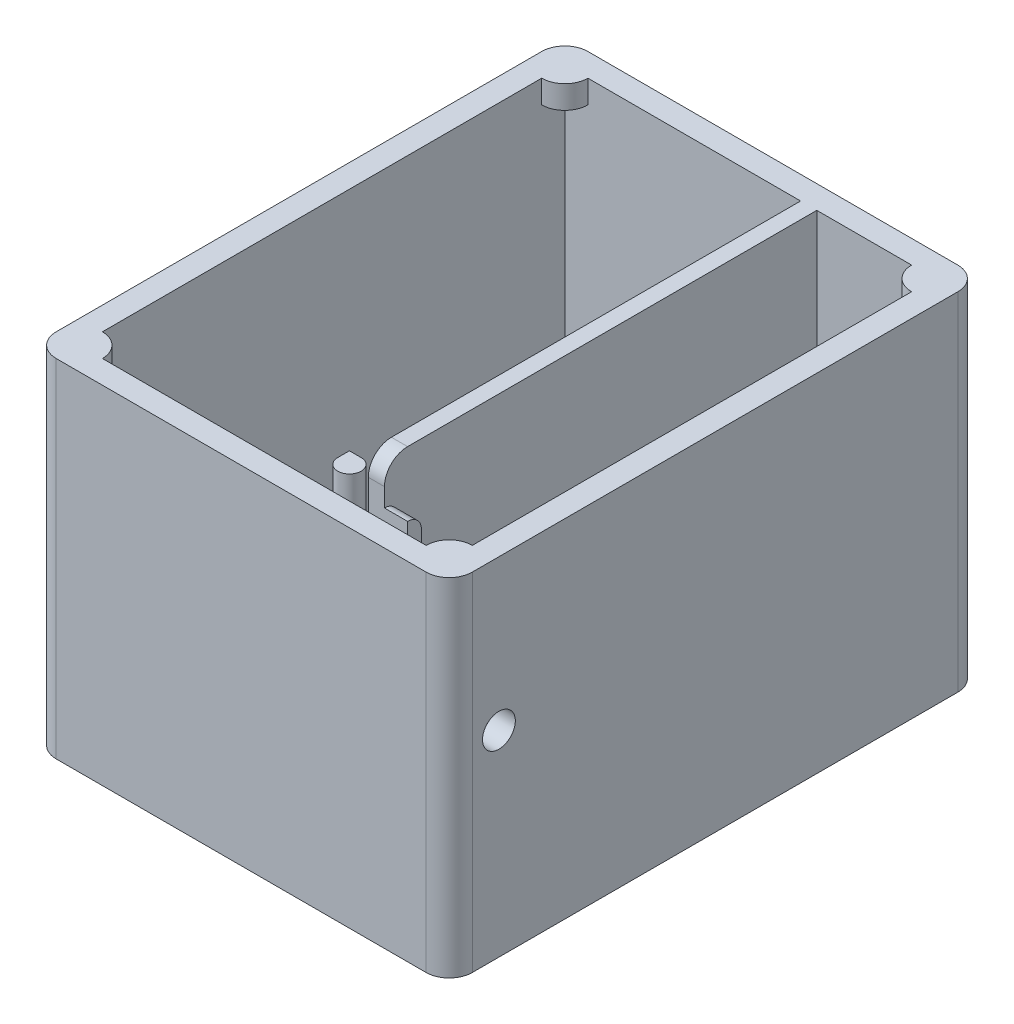
SolidWorks part; units mm, degrees
ref_plane "Front" through (0, 0, 0) normal (0, 0, 1) x (1, 0, 0)
ref_plane "Top" through (0, 0, 0) normal (0, 1, 0) x (1, 0, 0)
ref_plane "Right" through (0, 0, 0) normal (1, 0, 0) x (0, 0, -1)
sketch "Sketch1" plane through (0, 0, 0) normal (0, 1, 0) x (1, 0, 0)
  line L1 (-45, 57.5) -> (45, 57.5)
  line L2 (-45, 57.5) -> (-45, -57.5)
  line L3 (-45, -57.5) -> (45, -57.5)
  line L4 (45, 57.5) -> (45, -57.5)
  line L5 (-45, 57.5) -> (45, -57.5) construction
  line L6 (-45, -57.5) -> (45, 57.5) construction
  line L11 (-38.7302, 49.4886) -> (40.1958, -51.3613) construction
  point P0 (0, 0)
  point P5 (0, 0)
extrude "Boss-Extrude1" add sketch "Sketch1" along normal blind 70 contours L2 L1 L4 L3
sketch "Sketch2" plane through (0, 70, 0) normal (0, 1, 0) x (1, 0, 0)
  line L0 (40, -38) -> (40, -41) construction
  line L9 (14.5, 57.5) -> (14.5, -57.5) construction
  line L10 (40, 52.5) -> (14.5, 52.5)
  line L11 (40, 52.5) -> (40, -38)
  line L12 (40, -38) -> (14.5, -38)
  line L13 (40, 50) -> (40, 57.5) construction
  line L14 (14.5, 52.5) -> (14.5, -38)
  line L15 (-45, -41) -> (45, -41) construction
  line L16 (-45, 57.5) -> (45, 57.5) construction
  line L17 (45, 57.5) -> (45, -57.5) construction
  line L18 (40, 57.5) -> (40, 52.5) construction
  line L19 (-45, 57.5) -> (-45, -57.5) construction
  line L20 (40, 57.5) -> (40, -57.5) construction
  line L21 (-45, -57.5) -> (45, -57.5) construction
  line L27 (40, -57.5) -> (40, -52.5) construction
  line L28 (45, -52.5) -> (-45, -52.5) construction
  line L29 (45, 52.5) -> (-45, 52.5) construction
  point P0 (0, 0)
sketch "Sketch3" [suppressed] plane through (0, 70.016, 0) normal (0, 1, 0) x (1, 0, 0)
sketch "Sketch4" [suppressed] plane through (0, 70.016, 0) normal (0, 1, 0) x (1, 0, 0)
sketch "Sketch6" plane through (0, 70, 0) normal (0, 1, 0) x (1, 0, 0)
  line L3 (8, -52.5) -> (40, -52.5)
  line L4 (40, -41) -> (40, -52.5)
  line L6 (40, -41) -> (8, -41)
  line L8 (8, -41) -> (8, -52.5)
extrude "Cut-Extrude2" cut sketch "Sketch6" against normal blind 65.5
sketch "Sketch22" plane through (40, 0, 0) normal (-1, 0, 0) x (0, 0, 1)
  line L0 (52.5, 4.5) -> (52.5, 42.5) construction
  line L1 (52.5, 42.5) -> (46.75, 42.5) construction
  circle A0 centre (46.75, 42.5) radius 3.55
extrude "Cut-Extrude11" cut sketch "Sketch22" against normal through all both and the other way through all
extrude "Cut-Extrude12" cut sketch "Sketch2" against normal blind 65.5
sketch "Sketch23" plane through (0, 0, 38) normal (0, 0, -1) x (-1, 0, 0)
  line L2 (-40, 4.5) -> (-35, 4.5) construction
  line L3 (-35, 4.5) -> (-35, 10.5) construction
  line L5 (-19.5, 66) -> (-35, 66)
  line L6 (-19.5, 66) -> (-19.5, 10.5)
  line L7 (-19.5, 10.5) -> (-35, 10.5)
  line L8 (-35, 66) -> (-35, 10.5)
extrude "Cut-Extrude13" cut sketch "Sketch23" against normal blind 3
sketch "Sketch24" plane through (0, 0, 38) normal (0, 0, -1) x (-1, 0, 0)
  line L0 (-14.5, 70) -> (-14.5, 19.5) construction
  line L1 (-14.5, 4.5) -> (-14.5, 19.5) construction
  line L6 (-1.0248, 22.3804) -> (-21.5174, 18) construction
  line L7 (-17.8035, 50.536) -> (-18.2248, 54.4939) construction
  line L8 (-7.4826, 21) -> (-21.5174, 21)
  line L9 (-7.4826, 21) -> (-7.4826, 18)
  line L10 (-7.4826, 18) -> (-21.5174, 18)
  line L11 (-21.5174, 21) -> (-21.5174, 18)
  line L12 (-7.4826, 21) -> (-21.5174, 18) construction
  line L13 (-7.4826, 18) -> (-21.5174, 21) construction
extrude "Cut-Extrude14" cut sketch "Sketch24" against normal blind 3
fillet "Fillet2" radius 5 1 edges at (-45, 35, 57.5) type face fillet first side face at (0, 35, 57.5) second side face at (-45, 42.5, 50.3)
fillet "Fillet3" radius 5 1 edges at (45, 35, 57.5) type face fillet first side face at (45, 42.5, 50.3) second side face at (2.5, 35, 57.5)
fillet "Fillet4" radius 5 1 edges at (45, 35, -57.5) type face fillet first side face at (45, 42.5, 50.3) second side face at (0, 35, -57.5)
fillet "Fillet5" radius 5 1 edges at (-45, 35, -57.5) type face fillet first side face at (-2.5, 35, -57.5) second side face at (-45, 42.5, 50.3)
sketch "Sketch33" plane through (0, 0, 0) normal (0, -1, 0) x (1, 0, 0)
  line L0 (-45, -52.5) -> (-45, 52.5) construction
  line L1 (45, 57.4997) -> (-45, 57.4997)
  line L2 (45, 57.4997) -> (45, -57.4997)
  line L3 (45, -57.4997) -> (-45, -57.4997)
  line L4 (-45, 57.4997) -> (-45, -57.4997)
  line L5 (45, 57.4997) -> (-45, -57.4997) construction
  line L6 (45, -57.4997) -> (-45, 57.4997) construction
  point P0 (0, 0)
sketch "Sketch36" plane through (0, 70, 0) normal (0, 1, 0) x (1, 0, 0)
  line L0 (40, 34.925) -> (45, 34.925) construction
  line L1 (40, -38) -> (40, 52.5) construction
  line L2 (45, 52.5) -> (45, -52.5) construction
  line L3 (33.0194, 57.5) -> (33.0194, 52.5) construction
  line L4 (-40, 57.5) -> (40, 57.5) construction
  line L5 (40, 52.5) -> (14.5, 52.5) construction
  line L6 (25.7963, -52.5) -> (25.7963, -57.5) construction
  line L7 (8, -52.5) -> (40, -52.5) construction
  line L8 (-40, -57.5) -> (40, -57.5) construction
sketch "Sketch37" plane through (0, 70, 0) normal (0, 1, 0) x (1, 0, 0)
  line L0 (-26.557, 57.5) -> (-26.557, 52.5) construction
  line L1 (-40, 57.5) -> (40, 57.5) construction
  line L2 (-45, 49.7069) -> (-40, 49.7069) construction
  line L3 (-45, 52.5) -> (-45, -52.5) construction
  line L4 (-26.557, 52.5) -> (-40, 52.5) construction
  line L5 (-40, 52.5) -> (-40, 49.7069) construction
  line L6 (4.7483, -57.5) -> (4.7483, -52.5) construction
  line L7 (-40, -57.5) -> (40, -57.5) construction
  line L8 (-40, 52.5) -> (9, 52.5) construction
  line L10 (-40, 52.5) -> (11, 52.5)
  line L11 (-40, 52.5) -> (-40, -52.5)
  line L12 (-40, -52.5) -> (11, -52.5)
  line L13 (11, 52.5) -> (11, -52.5)
extrude "Cut-Extrude15" cut sketch "Sketch37" against normal blind 65.5
ref_plane "Plane1" through (-40, 70, -57.5) normal (1, 0, 0) x (0, 0, -1)
sketch "Sketch39" plane through (0, 4.5, 0) normal (0, 1, 0) x (1, 0, 0)
  line L0 (-40, -52.5) -> (-40, 5.92) construction
  line L1 (-40, 52.5) -> (-40, -52.5) construction
  line L2 (-40, 5.92) -> (10.8, 5.92) construction
  line L3 (10.8, 5.92) -> (10.8, -52.5) construction
  line L4 (-40, -52.5) -> (40, -52.5) construction
  line L5 (10.8, -52.5) -> (-40, -52.5) construction
  line L6 (10.8, -52.5) -> (8.26, -52.5) construction
  line L7 (-40, -52.5) -> (-37.46, -52.5) construction
  line L8 (10.8, 5.92) -> (8.26, 5.92)
  line L9 (-40, 5.92) -> (-37.46, 5.92)
  line L10 (-40, 5.92) -> (-40, 3.38)
  line L11 (10.8, 3.38) -> (8.26, 3.38) construction
  line L12 (-37.46, -52.5) -> (-40, -52.5)
  line L13 (-40, -52.5) -> (-40, -49.96)
  line L14 (10.8, 5.92) -> (10.8, 3.38)
  line L15 (10.8, -52.5) -> (8.26, -52.5)
  line L16 (10.8, -52.5) -> (10.8, -49.96)
  arc A4 (10.8, 3.38) -> (8.26, 5.92) centre (8.26, 3.38) cw
  arc A5 (10.8, -49.96) -> (8.26, -52.5) centre (8.26, -49.96) ccw
  arc A6 (-40, 3.38) -> (-37.46, 5.92) centre (-37.46, 3.38) ccw
  arc A7 (-37.46, -52.5) -> (-40, -49.96) centre (-37.46, -49.96) ccw
  line M3 (-40, 52.5) -> (-40, -52.5)
  line M4 (-40, -52.5) -> (40, -52.5)
sketch "Sketch40" plane through (11, 0, 0) normal (-1, 0, 0) x (0, 0, 1)
  line L0 (41, 4.5) -> (41, 26) construction
  line L1 (41, 70) -> (41, 21) construction
extrude "Boss-Extrude3" add sketch "Sketch39" along normal blind 21.5 contours L16 A5 M4 | A6 L9 M3 | A4 L8 L14 | A7 L13 L12 region at (8.3861, 4.5, 50.0861) region at (-37.5861, 4.5, -3.5061)
sketch "Sketch43" plane through (0, 26, 0) normal (0, 1, 0) x (1, 0, 0)
  line L0 (10.8, 3.38) -> (8.26, 3.38) construction
sketch "Sketch44" plane through (0, 70, 0) normal (0, 1, 0) x (1, 0, 0)
  circle A0 centre (40, 52.5) radius 5
  circle A1 centre (-40, 52.5) radius 5
  circle A2 centre (-40, -52.5) radius 5
  circle A3 centre (40, -52.5) radius 5
extrude "Boss-Extrude4" add sketch "Sketch44" along normal blind 5
sketch "Sketch48" plane through (0, 70, 0) normal (0, 1, 0) x (1, 0, 0)
  line L0 (-40, -57.5) -> (40, -57.5) construction
  line L1 (40, 57.5) -> (-40, 57.5)
  line L2 (40, 57.5) -> (40, 52.5)
  line L3 (40, 52.5) -> (-40, 52.5)
  line L4 (-40, 57.5) -> (-40, 52.5)
  line L5 (40, 52.5) -> (45, 52.5)
  line L6 (40, 52.5) -> (40, -52.5)
  line L7 (40, -52.5) -> (45, -52.5)
  line L8 (45, 52.5) -> (45, -52.5)
  line L9 (40, -57.5) -> (-40, -57.5)
  line L10 (40, -57.5) -> (40, -52.5)
  line L11 (40, -52.5) -> (-40, -52.5)
  line L12 (-40, -57.5) -> (-40, -52.5)
  line L14 (-40, -52.5) -> (-45, -52.5)
  line L15 (-40, -52.5) -> (-40, 52.5)
  line L16 (-40, 52.5) -> (-45, 52.5)
  line L17 (-45, -52.5) -> (-45, 52.5)
  arc M1 (40, -47.5) -> (45, -52.5) centre (40, -52.5) cw
  line M2 (45, -52.5) -> (45, 52.5)
  arc M3 (45, 52.5) -> (40, 47.5) centre (40, 52.5) cw
  line M4 (40, 47.5) -> (40, -38)
  line M14 (40, -41) -> (40, -47.5)
extrude "Boss-Extrude6" add sketch "Sketch48" along normal blind 5 contours L17 L14 L15 L16 | L6 M4 M14 M1 M2 M3 | L11 L12 L9 L10 | L4 L3 L2 L1 region at (-42.5, 70, 0) region at (42.5306, 70, 0)
sketch "Sketch53" plane through (0, 70, 0) normal (0, 1, 0) x (1, 0, 0)
  line L1 (11, -41) -> (14.5, -41)
  line L2 (11, -41) -> (11, 52.5)
  line L3 (11, 52.5) -> (14.5, 52.5)
  line L4 (14.5, -41) -> (14.5, 52.5)
extrude "Boss-Extrude7" add sketch "Sketch53" along normal blind 5
sketch "Sketch54" plane through (0, 70, 0) normal (0, 1, 0) x (1, 0, 0)
  line L1 (14.5, -38) -> (40, -38)
  line L2 (14.5, -38) -> (14.5, -41)
  line L3 (14.5, -41) -> (40, -41)
  line L4 (40, -38) -> (40, -41)
extrude "Cut-Extrude16" cut sketch "Sketch54" against normal blind 4
sketch "Sketch55" plane through (19.5, 0, 0) normal (1, 0, 0) x (0, 0, -1)
  line L1 (-38, 66) -> (-41, 66)
  line L2 (-38, 66) -> (-38, 63)
  arc A0 (-41, 66) -> (-38, 63) centre (-41, 63) cw
extrude "Cut-Extrude17" cut sketch "Sketch55" against normal blind 5 contours A0 L2 L1
sketch "Sketch56" plane through (35, 0, 0) normal (-1, 0, 0) x (0, 0, 1)
  line L1 (38, 66) -> (41, 66)
  line L2 (38, 66) -> (38, 63)
  arc A0 (38, 63) -> (41, 66) centre (41, 63) cw
extrude "Cut-Extrude18" cut sketch "Sketch56" against normal blind 5 contours L1 A0 L2
fillet "Fillet6" radius 5 1 edges at (12.75, 75, 41) type face fillet first side face at (0, 75, 0) second side face at (15, 54, 41)
sketch "Sketch57" plane through (0, 75, 0) normal (0, 1, 0) x (1, 0, 0)
  line L0 (14.5, -36) -> (14.5, -57.5) construction
  line L1 (40, -57.5) -> (-40, -57.5) construction
  line L2 (14.5, -36) -> (45, -36) construction
  line L3 (45, -52.5) -> (45, 52.5) construction
